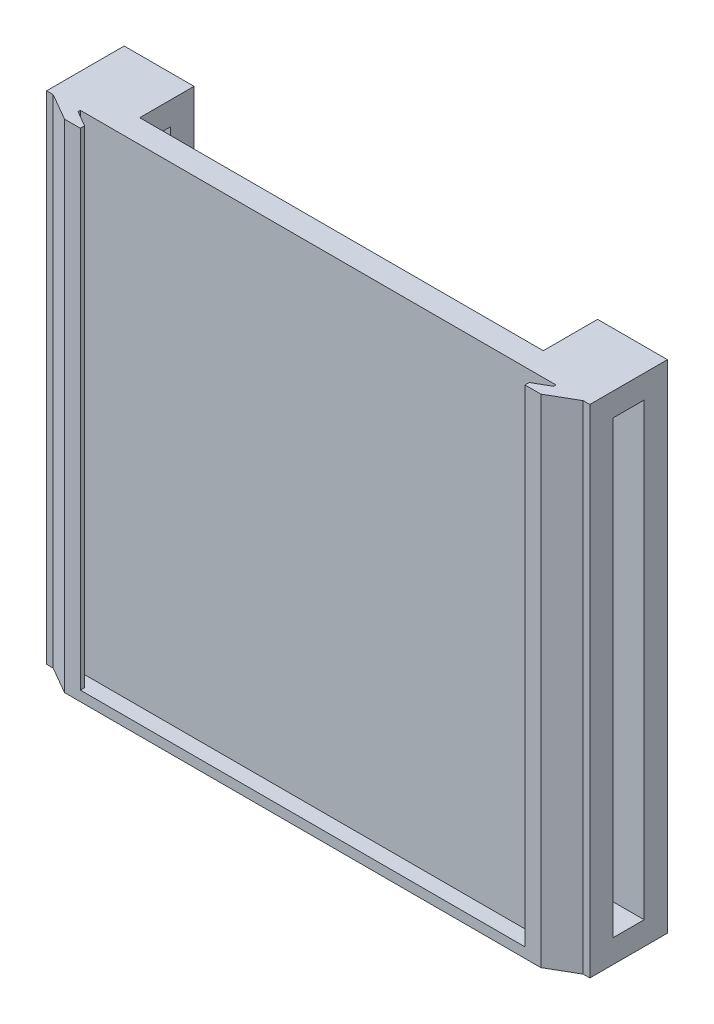
SolidWorks part; units mm, degrees
ref_plane "Front Plane" through (0, 0, 0) normal (0, 0, 1) x (1, 0, 0)
ref_plane "Top Plane" through (0, 0, 0) normal (0, 1, 0) x (1, 0, 0)
ref_plane "Right Plane" through (0, 0, 0) normal (1, 0, 0) x (0, 0, -1)
sketch "Sketch1" plane through (0, 0, 0) normal (0, 0, 1) x (1, 0, 0)
  line L0 (-35, 32) -> (35, -32) construction
  line L1 (-35, 32) -> (35, 32)
  line L2 (-35, 32) -> (-35, -32)
  line L3 (-35, -32) -> (35, -32)
  line L4 (35, 32) -> (35, -32)
  line L5 (-35, -32) -> (35, 32) construction
  point P4 (0, 0)
  dimension "D1" = 70
  dimension "D2" = 64
extrude "Boss-Extrude1" add sketch "Sketch1" along normal blind 10
sketch "Sketch2" plane through (0, 32, 0) normal (0, 1, 0) x (1, 0, 0)
  line L0 (28.6462, -12) -> (30.6821, -12)
  line L2 (35, -10) -> (-35, -10) construction
  line L3 (28.6462, -11.4547) -> (30.6462, -10.3)
  line L4 (30.6821, -12) -> (34.1462, -10)
  line L5 (27.442, -12) -> (30.442, -10.2679) construction
  line L6 (30.6462, -10.3) -> (30.6462, -10)
  line L8 (30.6462, -10) -> (34.1462, -10)
  line L9 (28.6462, -11.4547) -> (28.6462, -12)
  point P3 (30.6462, -10.15)
  dimension "D1" = 3.5
  dimension "D2" = 30.6462
  dimension "D3" = 2
  dimension "D4" = 0.3
  dimension "D5" = 2
extrude "Boss-Extrude2" add sketch "Sketch2" against normal through all
ref_plane "Plane1" through (0, 0, 0) normal (-1, 0, 0) x (0, 0, 1)
mirror "Mirror1" about plane through (0, 0, 0) normal (-1, 0, 0) of "Boss-Extrude2"
sketch "Sketch3" plane through (0, -32, 0) normal (0, -1, 0) x (1, 0, 0)
  line L0 (-28.6462, 11.4547) -> (-28.6462, 12) construction
  line L1 (-30.6462, 10.3) -> (-28.6462, 11.4547) construction
  line L2 (-30.6462, 10) -> (-30.6462, 10.3) construction
  line L3 (-30.6462, 10) -> (30.6462, 10) construction
  line L4 (30.6462, 10) -> (30.6462, 10.3) construction
  line L5 (30.6462, 10.3) -> (28.6462, 11.4547) construction
  line L6 (28.6462, 11.4547) -> (28.6462, 12) construction
  line L7 (-28.6462, 11.4547) -> (-28.6462, 12)
  line L8 (-30.6462, 10.3) -> (-28.6462, 11.4547)
  line L9 (-30.6462, 10) -> (-30.6462, 10.3)
  line L10 (-30.6462, 10) -> (30.6462, 10)
  line L11 (30.6462, 10) -> (30.6462, 10.3)
  line L12 (30.6462, 10.3) -> (28.6462, 11.4547)
  line L13 (28.6462, 11.4547) -> (28.6462, 12)
  line L14 (-28.6462, 12) -> (28.6462, 12)
extrude "Boss-Extrude3" add sketch "Sketch3" against normal blind 1.3 contours L14 L13 L12 L11 L10 L9 L8 L7
sketch "Sketch5" plane through (0, 32, 0) normal (0, 1, 0) x (1, 0, 0)
  line L0 (35, 0) -> (-35, 0) construction
  line L1 (-26, 0) -> (26, 0)
  line L2 (-26, 0) -> (-26, -7)
  line L3 (-26, -7) -> (26, -7)
  line L4 (26, 0) -> (26, -7)
  line L6 (-26, 0) -> (26, 0) construction
  line L7 (0, -7) -> (0, 0) construction
  dimension "D1" = 7
  dimension "D2" = 52
extrude "Cut-Extrude1" cut sketch "Sketch5" against normal through all
sketch "Sketch6" plane through (35, 0, 0) normal (1, 0, 0) x (0, 0, -1)
  line L4 (0, -32) -> (0, 32) construction
  line L5 (-3, 29) -> (-7, 29)
  line L6 (-3, 29) -> (-3, -29)
  line L7 (-3, -29) -> (-7, -29)
  line L8 (-7, 29) -> (-7, -29)
  line L9 (-10, -32) -> (0, -32) construction
  line L10 (-10, 32) -> (0, 32) construction
  dimension "D1" = 4
  dimension "D2" = 3
  dimension "D3" = 3
  dimension "D4" = 3
extrude "Cut-Extrude2" cut sketch "Sketch6" against normal through all
